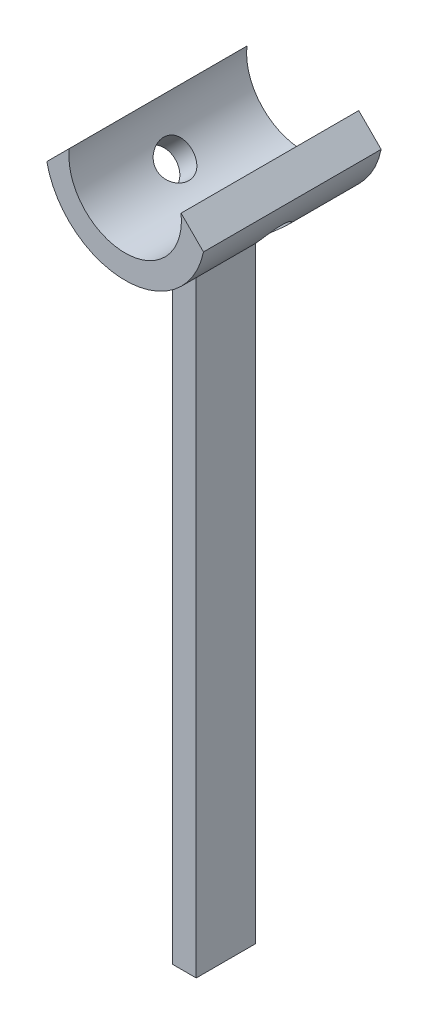
SolidWorks part; units mm, degrees
ref_plane "Front Plane" through (0, 0, 0) normal (0, 0, 1) x (1, 0, 0)
ref_plane "Top Plane" through (0, 0, 0) normal (0, 1, 0) x (1, 0, 0)
ref_plane "Right Plane" through (0, 0, 0) normal (1, 0, 0) x (0, 0, -1)
sketch "Sketch1" plane through (0, 0, 0) normal (0, 1, 0) x (1, 0, 0)
  line L1 (1, -12) -> (-1, -12)
  line L2 (1, -12) -> (1, -7)
  line L3 (1, -7) -> (-1, -7)
  line L4 (-1, -12) -> (-1, -7)
  dimension "D3" = 5
  dimension "D4" = 2
extrude "Boss-Extrude1" add sketch "Sketch1" against normal blind 55 contours L2 L3 L4 L1
sketch "Sketch2" plane through (0, 0, 0) normal (0, 0, 1) x (1, 0, 0)
  line L0 (-3.6183, 0) -> (3.4011, 0) construction
  line L1 (-8, 2) -> (8, 2) construction
  line L2 (-8, 2) -> (-4.4083, 5.5917)
  line L3 (8, 2) -> (3.6742, 6.3258)
  circle A0 centre (0, 4.75) radius 4.75
  circle A1 centre (0, 4.75) radius 6.75
  point P2 (-0.1086, 0)
  point P10 (4.0746, 6.3258)
  dimension "D1" = 0
  dimension "D3" = 2
  dimension "D4" = 45
  dimension "D5" = 45
  dimension "D6" = 8
  dimension "D7" = 8
  dimension "D2" = 2
extrude "Boss-Extrude2" add sketch "Sketch2" along normal blind 5 and the other way blind 10 from surface contours L2 A1 L3 A0 region at (-5.5591, 4.2274, 0) starting at face at (0, -27.5, 12)
ref_plane "Plane1" through (5, 5, 0) normal (0.7071, 0.7071, 0) x (0.7071, -0.7071, 0)
ref_plane "Plane2" through (-5.6066, -5.6066, 0) normal (-0.7071, -0.7071, 0) x (0.7071, -0.7071, 0)
sketch "Sketch4" plane through (-5.6066, -5.6066, 0) normal (-0.7071, -0.7071, 0) x (0.7071, -0.7071, 0)
  line L0 (0.6544, 7) -> (0.6544, 12) construction
  circle A0 centre (-3.3456, 9.5) radius 1.5
  point P4 (0.6544, 9.5)
  point P5 (0, 0)
  dimension "D1" = 4
extrude "Cut-Extrude1" cut sketch "Sketch4" against normal through all
mirror "Mirror1" about plane through (0, 0, 0) normal (1, 0, 0) of "Cut-Extrude1"
